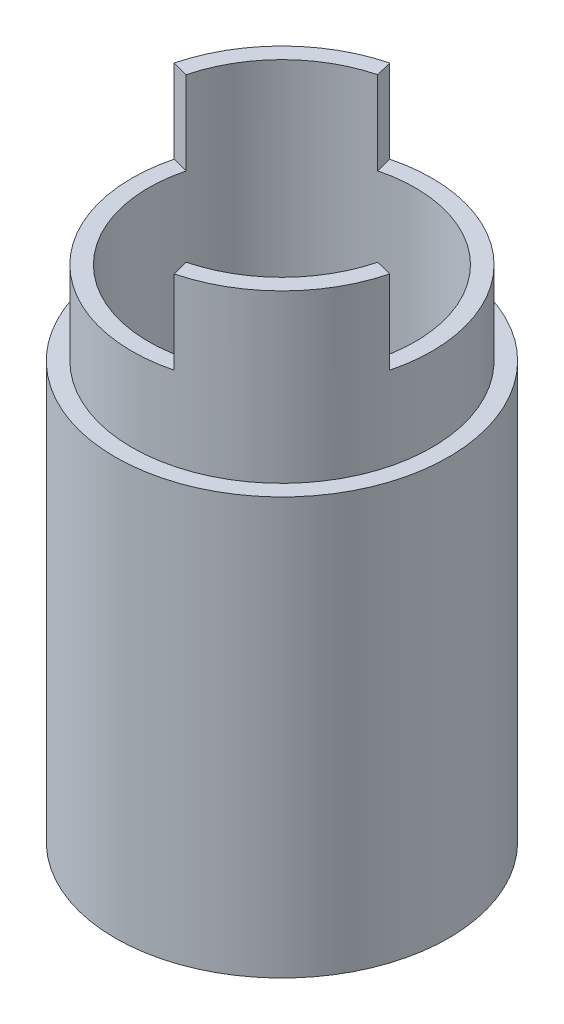
SolidWorks part; units mm, degrees
ref_plane "前视基准面" through (0, 0, 0) normal (0, 0, 1) x (1, 0, 0)
ref_plane "上视基准面" through (0, 0, 0) normal (0, 1, 0) x (1, 0, 0)
ref_plane "右视基准面" through (0, 0, 0) normal (1, 0, 0) x (0, 0, -1)
other "Configuration Table"
sketch "草图1" plane through (0, 0, 0) normal (0, 1, 0) x (1, 0, 0)
  circle A0 centre (0, 0) radius 20
  circle A1 centre (0, 0) radius 16
  dimension "D1" = 40
  dimension "D2" = 32
extrude "凸台-拉伸1" add sketch "草图1" along normal blind 50
sketch "草图3" plane through (0, 0, 0) normal (0, 1, 0) x (1, 0, 0)
  circle A0 centre (0, 0) radius 18
  circle A1 centre (0, 0) radius 16 construction
  circle A2 centre (0, 0) radius 16
  dimension "D1" = 36
extrude "凸台-拉伸2" add sketch "草图3" along normal blind 10 from offset 50
sketch "草图4" plane through (0, 0, 0) normal (0, 1, 0) x (1, 0, 0)
  line L0 (-1000, 0) -> (49000, 0) construction
  line L1 (0, -1000) -> (0, 49000) construction
  line L2 (-15.4919, -4) -> (-15.4919, 4) construction
  line L3 (0, 0) -> (-48412.2918, 12500) construction
  line L4 (0, 0) -> (-48412.2918, -12500) construction
  line L5 (-15.4919, 4) -> (-17.4284, 4.5)
  line L6 (-15.4919, -4) -> (-17.4284, -4.5)
  line L7 (15.4919, 4) -> (17.4284, 4.5)
  line L8 (15.4919, -4) -> (17.4284, -4.5)
  line L9 (-4, 15.4919) -> (4, 15.4919)
  line L10 (0, 0) -> (12500, 48412.2918) construction
  line L11 (0, 0) -> (-12500, 48412.2918) construction
  line L12 (-4.5, 17.4284) -> (-4, 15.4919)
  line L13 (4.5, 17.4284) -> (4, 15.4919)
  line L14 (-4, -15.4919) -> (-4.5, -17.4284)
  line L15 (4, -15.4919) -> (4.5, -17.4284)
  circle A0 centre (0, 0) radius 16
  circle A1 centre (0, 0) radius 18
  point P11 (-15.4919, 0)
  point P24 (0, 15.4919)
  dimension "D1" = 32
  dimension "D2" = 36
  dimension "D3" = 8
  dimension "D4" = 8
extrude "凸台-拉伸3" add sketch "草图4" along normal blind 10 from offset 60 contours L12 A1 L5 A0 | L15 A1 L8 A0 region at (-11.4735, 0, -11.4735) region at (11.4735, 0, 11.4735)
